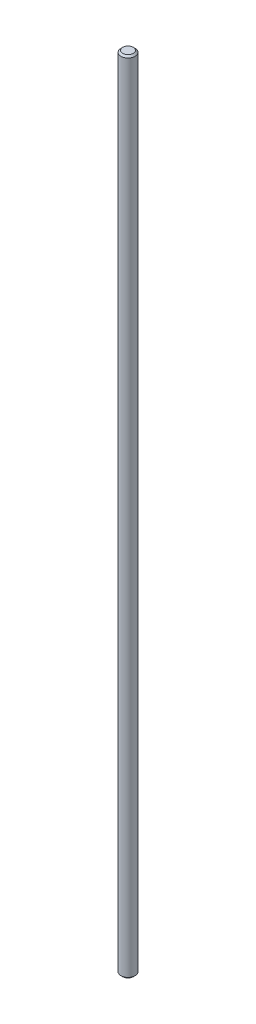
SolidWorks part; units mm, degrees
material "Plain Carbon Steel"
ref_plane "Front Plane" through (0, 0, 0) normal (0, 0, 1) x (1, 0, 0)
ref_plane "Top Plane" through (0, 0, 0) normal (0, 1, 0) x (1, 0, 0)
ref_plane "Right Plane" through (0, 0, 0) normal (1, 0, 0) x (0, 0, -1)
sketch "Sketch1" plane through (0, 0, 0) normal (0, 1, 0) x (1, 0, 0)
  circle A0 centre (0, 0) radius 4
  dimension "D1" = 8
extrude "Boss-Extrude1" add sketch "Sketch1" along normal blind 455
chamfer "Chamfer1" distance 1 angle 45 2 edges at (0, 455, 4) (0, 0, 4)
